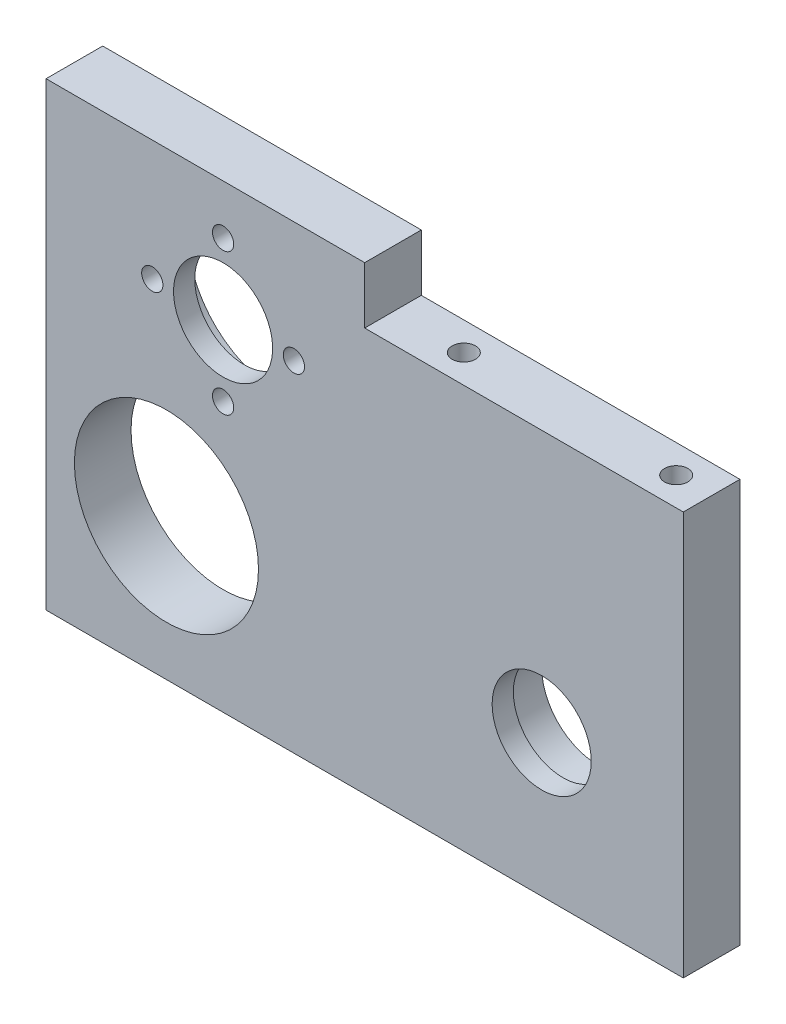
SolidWorks part; units mm, degrees
ref_plane "Front" through (0, 0, 0) normal (0, 0, 1) x (1, 0, 0)
ref_plane "Top" through (0, 0, 0) normal (0, 1, 0) x (1, 0, 0)
ref_plane "Right" through (0, 0, 0) normal (1, 0, 0) x (0, 0, -1)
sketch "Esquisse1" plane through (0, 0, 0) normal (0, 0, 1) x (1, 0, 0)
  line L1 (0, 0) -> (90, 0)
  line L2 (0, 0) -> (0, 65)
  line L3 (0, 65) -> (90, 65)
  line L4 (90, 0) -> (90, 65)
  circle A0 centre (70, 20) radius 7
  circle A1 centre (17, 20) radius 13
  circle A2 centre (25, 48) radius 13
  dimension "D3" = 14
  dimension "D4" = 20
  dimension "D6" = 53
  dimension "D8" = 26
  dimension "D9" = 26
  dimension "D1" = 90
  dimension "D2" = 65
  dimension "D5" = 70
  dimension "D7" = 20
  dimension "D10" = 53
  dimension "D11" = 48
extrude "Boss.-Extru.1" add sketch "Esquisse1" along normal blind 8
sketch "Esquisse2" plane through (0, 0, 0) normal (0, 0, -1) x (-1, 0, 0)
  circle A0 centre (-25, 48) radius 13
  circle A1 centre (-17, 20) radius 13 construction
extrude "Boss.-Extru.2" add sketch "Esquisse2" along normal blind 3 from surface starting at face at (45, 32.5, 8)
sketch "Esquisse3" plane through (0, 0, 5) normal (0, 0, -1) x (-1, 0, 0)
  line L0 (-15, 48) -> (-25, 48) construction
  circle A0 centre (-25, 48) radius 7
  circle A1 centre (-15, 48) radius 1.5
  circle A2 centre (-25, 38) radius 1.5
  circle A3 centre (-35, 48) radius 1.5
  circle A4 centre (-25, 58) radius 1.5
  point P13 (-25, 48)
  dimension "D1" = 14
  dimension "D2" = 3
  dimension "D3" = 10
  dimension "D4" = 4
extrude "Enlèv. mat.-Extru.1" cut sketch "Esquisse3" against normal through all
sketch "Esquisse4" plane through (0, 0, 8) normal (0, 0, 1) x (1, 0, 0)
  circle A0 centre (70, 20) radius 8
  dimension "D1" = 16
extrude "Enlèv. mat.-Extru.2" cut sketch "Esquisse4" along normal blind 5 from surface starting at face at (30, 20, 0)
sketch "Esquisse5" plane through (0, 0, 0) normal (0, 0, -1) x (-1, 0, 0)
  line L1 (-90, 65) -> (-45, 65)
  line L2 (-90, 65) -> (-90, 57)
  line L3 (-90, 57) -> (-45, 57)
  line L4 (-45, 65) -> (-45, 57)
  dimension "D1" = 8
  dimension "D2" = 45
extrude "Enlèv. mat.-Extru.3" cut sketch "Esquisse5" against normal through all
sketch "Esquisse6" plane through (0, 0, 0) normal (-1, 0, 0) x (0, 0, 1)
  line L0 (4, 0) -> (4, 45) construction
  line L1 (8, 0) -> (0, 0) construction
  circle A0 centre (4, 45) radius 1.65
  circle A1 centre (4, 7) radius 1.65
  dimension "D1" = 3.3
  dimension "D2" = 38
  dimension "D3" = 7
extrude "Enlèv. mat.-Extru.4" cut sketch "Esquisse6" against normal blind 10
sketch "Esquisse7" plane through (0, 57, 0) normal (0, 1, 0) x (1, 0, 0)
  line L0 (45, -4) -> (85, -4) construction
  line L1 (45, -8) -> (45, 0) construction
  circle A0 centre (85, -4) radius 1.65
  circle A1 centre (55, -4) radius 1.65
  dimension "D1" = 30
  dimension "D2" = 3.3
  dimension "D3" = 10
extrude "Enlèv. mat.-Extru.5" cut sketch "Esquisse7" against normal blind 10
